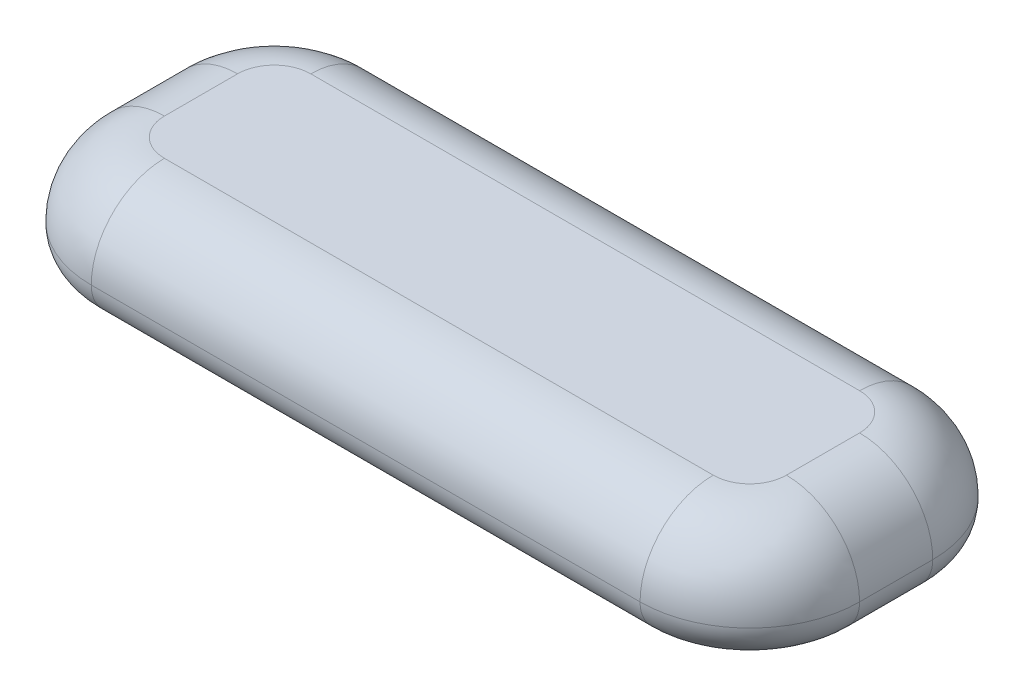
SolidWorks part; units mm, degrees
ref_plane "前视基准面" through (0, 0, 0) normal (0, 0, 1) x (1, 0, 0)
ref_plane "上视基准面" through (0, 0, 0) normal (0, 1, 0) x (1, 0, 0)
ref_plane "右视基准面" through (0, 0, 0) normal (1, 0, 0) x (0, 0, -1)
sketch "草图1" plane through (0, 0, 0) normal (0, 1, 0) x (1, 0, 0)
  line L1 (-37.5, 15) -> (37.5, 15)
  line L2 (-47.5, 5) -> (-47.5, -5)
  line L3 (-37.5, -15) -> (37.5, -15)
  line L4 (47.5, 5) -> (47.5, -5)
  line L5 (0, -15) -> (0, 15) construction
  line L6 (-47.5, 0) -> (47.5, 0) construction
  arc A0 (-47.5, -5) -> (-37.5, -15) centre (-37.5, -5) ccw
  arc A1 (-47.5, 5) -> (-37.5, 15) centre (-37.5, 5) cw
  arc A2 (37.5, 15) -> (47.5, 5) centre (37.5, 5) cw
  arc A3 (47.5, -5) -> (37.5, -15) centre (37.5, -5) cw
  point P0 (0, 0)
  point P8 (-47.5, 15)
  point P11 (47.5, 15)
  point P15 (47.5, -15)
  dimension "D3" = 10
  dimension "D1" = 95
  dimension "D2" = 30
extrude "凸台-拉伸1" add sketch "草图1" along normal blind 10
shell "抽壳2" thickness 5 removed face at (0, 0, 0) outward yes
fillet "圆角3" radius 10 8 edges at (48.1066, 15, -15.6066) (52.5, 15, 0) (48.1066, 15, 15.6066) (0, 15, 20) (-48.1066, 15, 15.6066) (-52.5, 15, 0) (-48.1066, 15, -15.6066) (0, 15, -20)
fillet "圆角4" radius 5 8 edges at (52.5, 0, 0) (48.1066, 0, 15.6066) (0, 0, 20) (-48.1066, 0, 15.6066) (-52.5, 0, 0) (-48.1066, 0, -15.6066) (0, 0, -20) (48.1066, 0, -15.6066)
ref_plane "基准面1" through (0, 10, 0) normal (0, -1, 0) x (-1, 0, 0)
sketch "草图2" plane through (0, 10, 0) normal (0, -1, 0) x (-1, 0, 0)
  line L0 (0, 0) -> (37, 0) construction
  line L1 (0, 0) -> (0, 6.5357) construction
  line L2 (34.825, 0.7) -> (39.175, 0.7)
  line L3 (34.825, 0.7) -> (34.825, -0.7)
  line L4 (34.825, -0.7) -> (39.175, -0.7)
  line L5 (39.175, 0.7) -> (39.175, -0.7)
  line L6 (37, -0.7) -> (37, 0.7) construction
  line L7 (34.825, 0) -> (39.175, 0) construction
  line L8 (36.3, 2.175) -> (37.7, 2.175)
  line L9 (36.3, 2.175) -> (36.3, -2.175)
  line L10 (36.3, -2.175) -> (37.7, -2.175)
  line L11 (37.7, 2.175) -> (37.7, -2.175)
  line L12 (37, -2.175) -> (37, 2.175) construction
  line L13 (36.3, 0) -> (37.7, 0) construction
  line L14 (-36.3, 0) -> (-37.7, 0) construction
  line L15 (-37, -2.175) -> (-37, 2.175) construction
  line L16 (-34.825, 0) -> (-39.175, 0) construction
  line L17 (-37, -0.7) -> (-37, 0.7) construction
  line L18 (-37.7, 2.175) -> (-37.7, -2.175)
  line L19 (-36.3, -2.175) -> (-37.7, -2.175)
  line L20 (-36.3, 2.175) -> (-36.3, -2.175)
  line L21 (-36.3, 2.175) -> (-37.7, 2.175)
  line L22 (-39.175, 0.7) -> (-39.175, -0.7)
  line L23 (-34.825, -0.7) -> (-39.175, -0.7)
  line L24 (-34.825, 0.7) -> (-34.825, -0.7)
  line L25 (-34.825, 0.7) -> (-39.175, 0.7)
  circle A0 centre (37, 0) radius 2.8
  circle A1 centre (-37, 0) radius 2.8
  dimension "D2" = 5.6
  dimension "D1" = 37
  dimension "D3" = 4.35
  dimension "D4" = 1.4
  dimension "D5" = 4.35
  dimension "D6" = 1.4
extrude "凸台-拉伸2" add sketch "草图2" along normal blind 8 contours A0 L8 L11 L2 L5 L4 L10 L9 L3 | A1 L25 L24 L23 L20 L19 L18 L22 L21 region at (-34.2792, 10, 0) region at (39.7208, 10, 0)
